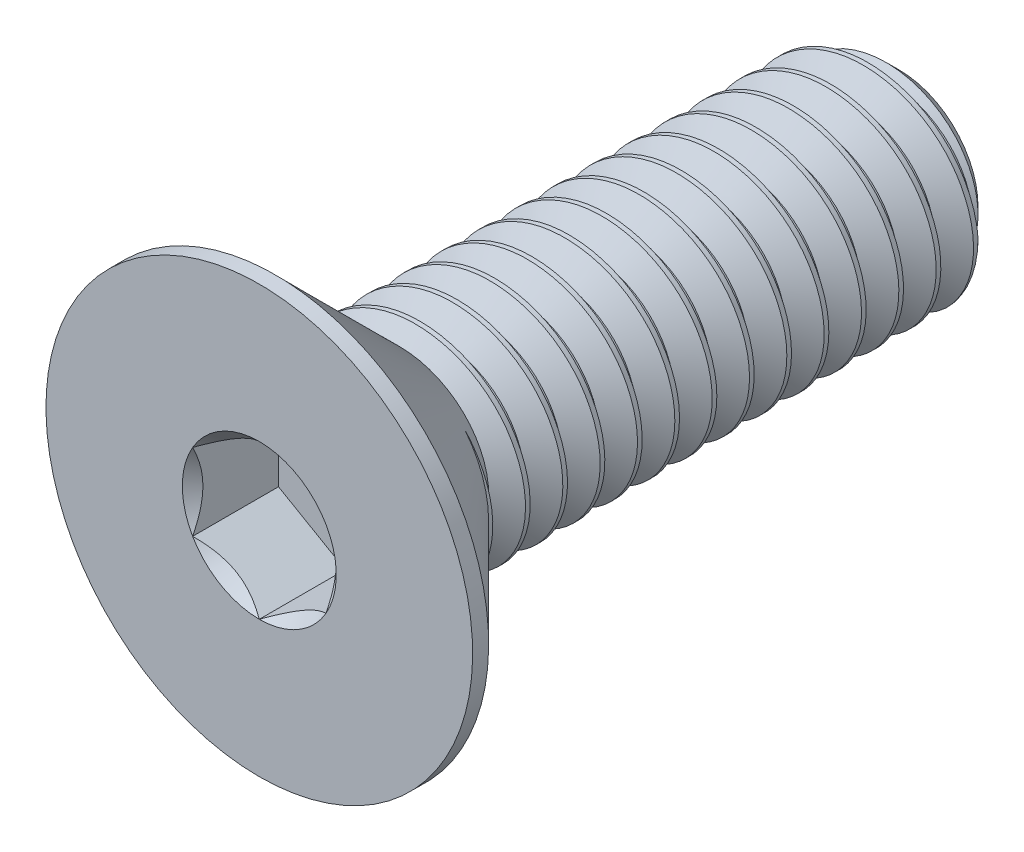
SolidWorks part; units mm, degrees
ref_plane "Front" through (0, 0, 0) normal (0, 0, 1) x (1, 0, 0)
ref_plane "Top" through (0, 0, 0) normal (0, 1, 0) x (1, 0, 0)
ref_plane "Right" through (0, 0, 0) normal (1, 0, 0) x (0, 0, -1)
sketch "Sketch1" plane through (0, 0, 0) normal (1, 0, 0) x (0, 0, -1)
  line L0 (0, 4) -> (0.3, 4) construction
  line L1 (0.3, 4) -> (2.3, 2) construction
  line L2 (0, 2) -> (12, 2)
  line L3 (12, 2) -> (12, 0)
  line L4 (12, 0) -> (0, 0)
  line L5 (0, 0) -> (0, 4) construction
  line L6 (0, 4) -> (0, -4) construction
  line L7 (12, 2) -> (12, -2) construction
  line L8 (0, -4) -> (0.3, -4) construction
  line L9 (0.3, -4) -> (2.3, -2) construction
  line L11 (0, 2) -> (0, 0)
  line L12 (2.3, 2) -> (2.3, 0) construction
revolve "Revolve1" add sketch "Sketch1" angle 360 mid plane about L4
sketch "Sketch3" plane through (0, 0, -12) normal (0, 0, -1) x (-1, 0, 0)
  circle A0 centre (0, 0) radius 2
curve "Helix/Spiral1" pitch 0.7 height 12 radius 2 centre (0, 0, -12) axis (0, 0, 1) start towards (0, 1, 0)
sketch "Sketch2" plane through (0, 0, 0) normal (1, 0, 0) x (0, 0, -1)
  line L0 (12, 2) -> (12.6125, 2)
  line L1 (12.6125, 2) -> (12.35, 1.5453)
  line L2 (12.35, 1.5453) -> (12.2625, 1.5453)
  line L3 (12.2625, 1.5453) -> (12, 2)
  line L4 (12.1312, 1.7727) -> (12.4812, 1.7727) construction
  dimension "D1" = 60
  dimension "D2" = 0.0875
  dimension "D3" = 0.35
chamfer "Chamfer1" distance 0.525 angle 45 1 edges at (0, 2, -12)
sweep "Cut-Sweep1" cut profiles "Sketch2" path "Helix/Spiral1" align with end faces yes
sketch "Sketch7" plane through (0, 0, 0) normal (1, 0, 0) x (0, 0, -1)
  line L0 (0, 4) -> (0.3, 4) construction
  line L1 (0.3, 4) -> (2.3, 2) construction
  line L2 (0, 4) -> (0.3, 4)
  line L3 (0.3, 4) -> (2.3, 2)
  line L4 (2.3, 2) -> (2.3, 0) construction
  line L5 (2.3, 2) -> (2.3, 0)
  line L7 (0, 0) -> (0, 4) construction
  line L8 (0, 0) -> (0, 4)
  line L9 (0, 0) -> (2.3, 0)
  line L10 (4.4, 0) -> (-4.4, 0) construction
revolve "Revolve2" add sketch "Sketch7" angle 360 mid plane about L9
ref_plane "Plane1" through (0, 0, -2.3) normal (0, 0, 1) x (1, 0, 0)
sketch "Sketch8" plane through (0, 0, -2.3) normal (0, 0, 1) x (1, 0, 0)
  circle A0 centre (0, 0) radius 2
extrude "Boss-Extrude1" add sketch "Sketch8" against normal through all draft 45
sketch "Sketch5" plane through (0, 0, 0) normal (0, 0, 1) x (1, 0, 0)
  line L1 (1.25, -0.7217) -> (1.25, 0.7217)
  line L2 (1.25, 0.7217) -> (0, 1.4434)
  line L3 (0, 1.4434) -> (-1.25, 0.7217)
  line L4 (-1.25, 0.7217) -> (-1.25, -0.7217)
  line L5 (-1.25, -0.7217) -> (0, -1.4434)
  line L6 (0, -1.4434) -> (1.25, -0.7217)
  circle A0 centre (0, 0) radius 1.25 construction
  dimension "Hex" = 2.5
extrude "Cut-Extrude2" cut sketch "Sketch5" against normal blind 1.61
sketch "Sketch6" plane through (0, 0, 0) normal (0, 0, 1) x (1, 0, 0)
  circle A0 centre (0, 0) radius 1.4434
extrude "Cut-Extrude3" cut sketch "Sketch6" against normal blind 1.61 draft 45
sketch "Sketch9" [suppressed] plane through (0, 0, -1.5) normal (0, 0, 1) x (1, 0, 0)
  circle A1 centre (0, 0) radius 1.25
  circle A2 centre (0, 0) radius 1.25
  point P0 (0, 1.25)
  dimension "D1" = 0
extrude "Boss-Extrude2" [suppressed] add sketch "Sketch9" against normal offset from surface (3.5 mm away) 26 up to face at (0, 1.475, -12)
fillet "Fillet1" [suppressed] radius 0.4
sketch "Sketch10" plane through (0, 0, 0) normal (1, 0, 0) x (0, 0, -1)
  line L0 (12, 2) -> (12, -2) construction
  point P0 (10.95, -2)
  dimension "D1" = 1.05
equation "\"D3@Helix/Spiral1\" = \"Lg@Sketch1\""
equation "\"D2@Sketch2\" = \"D4@Helix/Spiral1\" * .125"
equation "\"D3@Sketch2\" = \"D4@Helix/Spiral1\" * .5"
equation "\"D1@Chamfer1\" = \"D4@Helix/Spiral1\" * .75"
equation "\"D1@Cut-Extrude2\" = \"Head Ht@Sketch1\" * .7"
equation "\"D1@Sketch10\" = \"D4@Helix/Spiral1\" * 1.5"
equation "\"D1@Cut-Extrude3\" = \"D1@Cut-Extrude2\""
equation "\"D1@Fillet1\" = \"Dia@Sketch1\" * .1"
